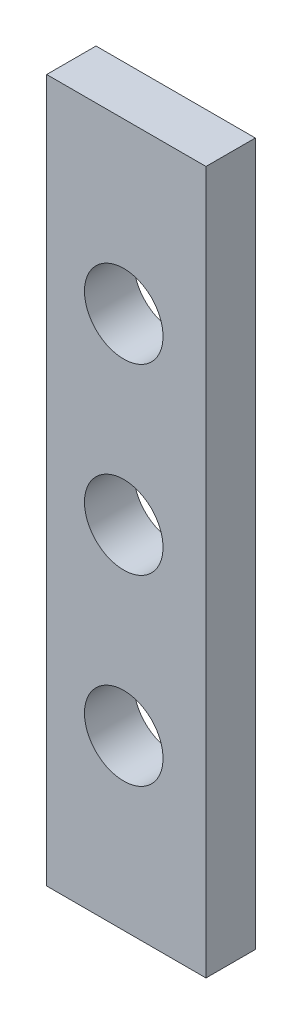
SolidWorks part; units mm, degrees
ref_plane "前视基准面" through (0, 0, 0) normal (0, 0, 1) x (1, 0, 0)
ref_plane "上视基准面" through (0, 0, 0) normal (0, 1, 0) x (1, 0, 0)
ref_plane "右视基准面" through (0, 0, 0) normal (1, 0, 0) x (0, 0, -1)
sketch "草图1" plane through (0, 0, 0) normal (0, 0, 1) x (1, 0, 0)
  line L6 (-130, -105) -> (-121.2816, -105)
  line L7 (-130, -105) -> (-130, -66.5374)
  line L8 (-130, -66.5374) -> (-121.2816, -66.5374)
  line L9 (-121.2816, -105) -> (-121.2816, -66.5374)
extrude "凸台-拉伸1" add sketch "草图1" along normal blind 2.7
hole_wizard "打孔尺寸(%根据十字)槽沉头木螺钉的类型1" positions "草图2" profile "草图3" countersink size "M4" standard "GB"
sketch "草图2" plane through (40.4914, -131.0101, 7) normal (0, 0, 1) x (0, 1, 0)
  point P0 (35.2414, 166.273)
  point P3 (45.2414, 166.273)
  point P6 (55.2414, 166.273)
  point P9 (206.7788, 166.273)
  point P12 (216.7788, 166.273)
  point P15 (226.7788, 166.273)
sketch "草图3" plane through (-125.7816, -95.7687, 7) normal (1, 0, 0) x (0, -1, 0)
  line L0 (0, 0) -> (0, 20.2919)
  line L1 (0, 20.2919) -> (2.15, 19)
  line L2 (2.15, 19) -> (2.15, 1.85)
  line L3 (2.15, 1.85) -> (4, 0)
  line L4 (4, 0) -> (0, 0)
  line L5 (-2.15, 1.85) -> (-4, 0) construction
  line L6 (0, 20.2919) -> (-2.15, 19) construction
  line L7 (0, -6.35) -> (0, 107.95) construction
  dimension "孔直径" = 4.3
  dimension "孔深度" = 19
  dimension "近端锥形沉头孔直径" = 8
  dimension "近端锥形沉头孔角度" = 90
  dimension "导头角度" = 118
